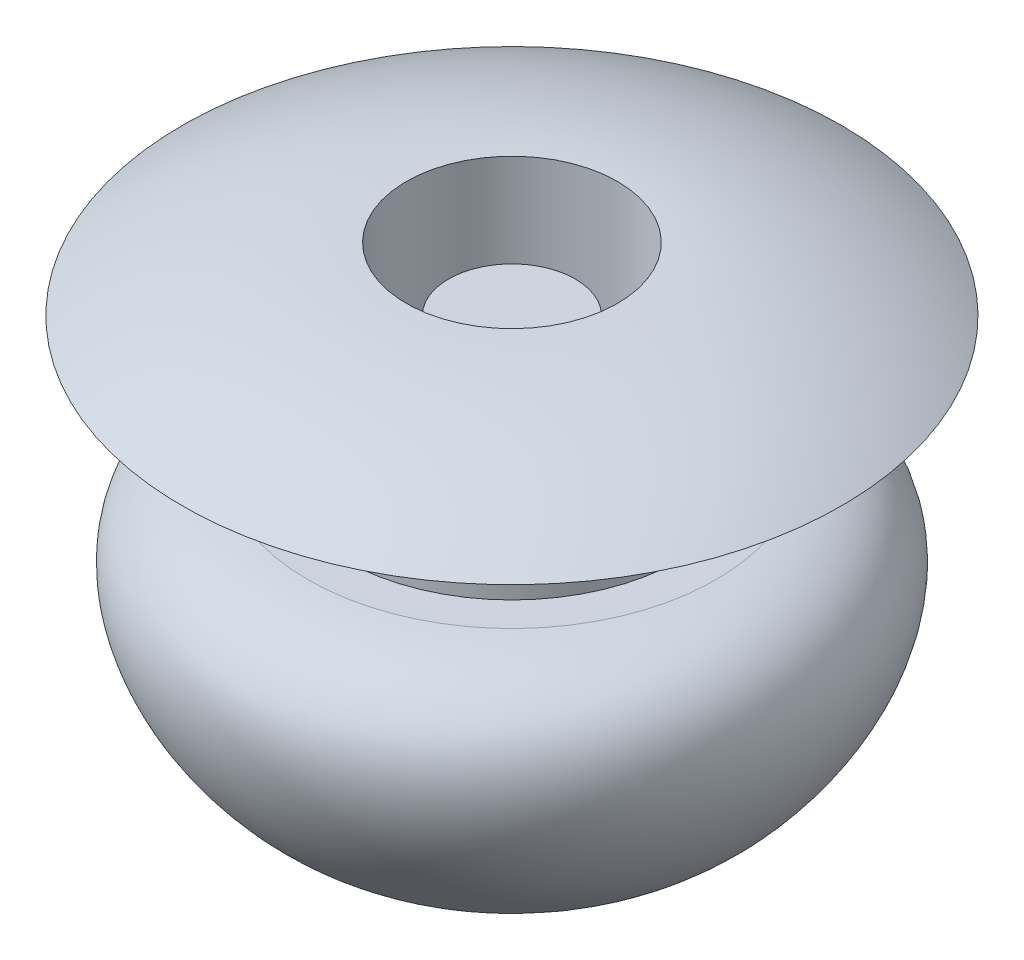
SolidWorks part; units mm, degrees
material "AISI 316 Stal nierdzewna odprężona (SS)"
ref_plane "Płaszczyzna przednia" through (0, 0, 0) normal (0, 0, 1) x (1, 0, 0)
ref_plane "Płaszczyzna górna" through (0, 0, 0) normal (0, 1, 0) x (1, 0, 0)
ref_plane "Płaszczyzna prawa" through (0, 0, 0) normal (1, 0, 0) x (0, 0, -1)
sketch "Szkic1" plane through (0, 0, 0) normal (1, 0, 0) x (0, 0, -1)
  line L1 (0, 0) -> (-0.75, 0)
  line L2 (-0.75, 0) -> (-0.75, -1.7007)
  line L3 (-0.75, -1.7007) -> (-1.25, -1.7007)
  line L4 (-1.25, -1.7007) -> (-1.25, 0.75)
  line L5 (-3.9, 0) -> (-2, 0)
  line L6 (-2, 0) -> (-2, -1.5)
  line L7 (-2, -1.5) -> (-2.4139, -1.5)
  line L8 (0, 0) -> (0, 0.4842) construction
  line L9 (0, -1.7007) -> (0, 0)
  line L10 (0, -1.7007) -> (0, -3.2007)
  line L11 (66.2841, -1.5) -> (70.2841, -1.5) construction
  arc A0 (-1.25, 0.75) -> (-3.9, 0) centre (-1.25, -4.3067) ccw
  ellipse E0 centre (0, -2.4507) end of major axis (-1.75, -2.4507) minor radius 0.75 (-0.956, -3.0789) -> (0, -3.2007) ccw
  spline S0 degree 3 poles (-2.4139, -1.5) (-3.8675, -1.6697) (-3.5289, -3.802) (-1.084, -5.3735) (-0.2718, -3.375) (-0.956, -3.0789) knots 0 0 0 0 0.464993 0.721928 1 1 1 1
  dimension "D1" = 7.8
  dimension "D2" = 2.5
  dimension "D3" = 4
  dimension "D4" = 0.75
  dimension "D5" = 1.5
  dimension "D6" = 1.5
  dimension "D7" = 3.5
  dimension "D8" = 3.1855
  dimension "D9" = 2.5026
  dimension "D10" = 1.9
  dimension "D11" = 1.5789
  dimension "D12" = 0.5792
  dimension "D13" = 4.8278
  dimension "D14" = 3.3858
  dimension "D15" = 2.8395
  dimension "D16" = 1.25
  dimension "D17" = 0.6409
  dimension "D18" = 0.956
revolve "Obrót1" add sketch "Szkic1" angle 360 about L8
